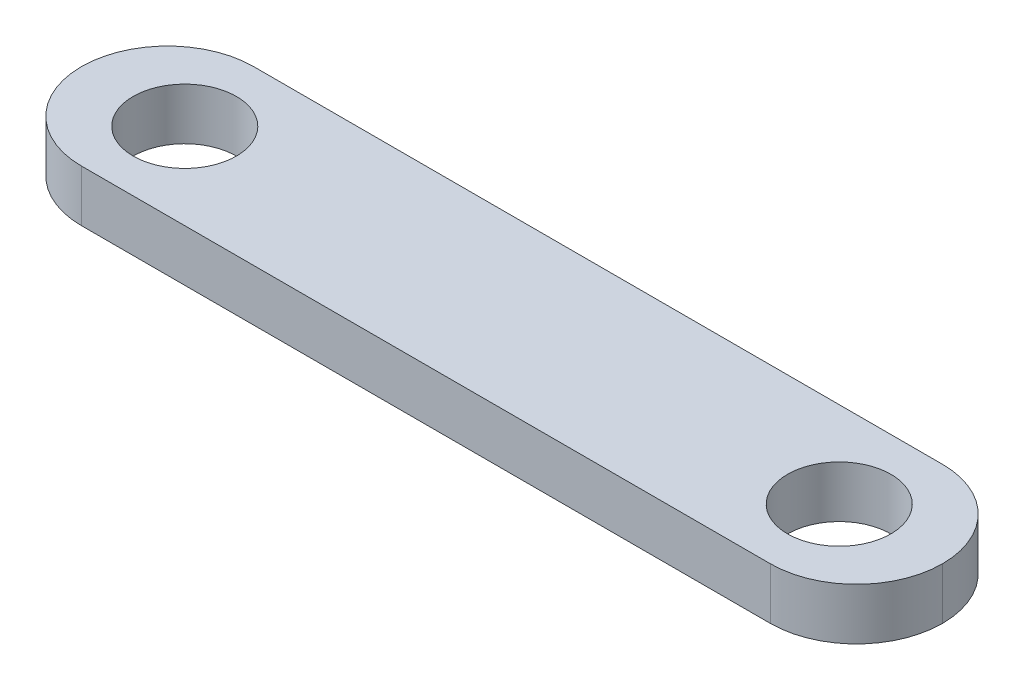
SolidWorks part; units mm, degrees
ref_plane "Front Plane" through (0, 0, 0) normal (0, 0, 1) x (1, 0, 0)
ref_plane "Top Plane" through (0, 0, 0) normal (0, 1, 0) x (1, 0, 0)
ref_plane "Right Plane" through (0, 0, 0) normal (1, 0, 0) x (0, 0, -1)
sketch "Sketch2" plane through (0, 0, 0) normal (0, 1, 0) x (1, 0, 0)
  line L1 (0, 0) -> (50, 0)
  line L2 (0, 0) -> (0, 10)
  line L3 (0, 10) -> (50, 10)
  line L4 (50, 0) -> (50, 10)
  dimension "D1" = 50
  dimension "D2" = 10
extrude "Boss-Extrude1" add sketch "Sketch2" along normal blind 3
fillet "Fillet1" radius 5 2 edges at (0, 1.5, -10) (0, 1.5, 0)
fillet "Fillet2" radius 5 2 edges at (50, 1.5, -10) (50, 1.5, 0)
sketch "Sketch9" plane through (0, 3, 0) normal (0, 1, 0) x (1, 0, 0)
  line L0 (45, 10) -> (5, 10) construction
  circle A0 centre (6, 5) radius 3
  dimension "D1" = 5
  dimension "D2" = 6
extrude "Cut-Extrude2" cut sketch "Sketch9" against normal through all
sketch "Sketch10" plane through (0, 3, 0) normal (0, 1, 0) x (1, 0, 0)
  line L0 (45, 10) -> (5, 10) construction
  circle A0 centre (44, 5) radius 3
  dimension "D1" = 5
  dimension "D2" = 6
extrude "Cut-Extrude3" cut sketch "Sketch10" against normal through all
